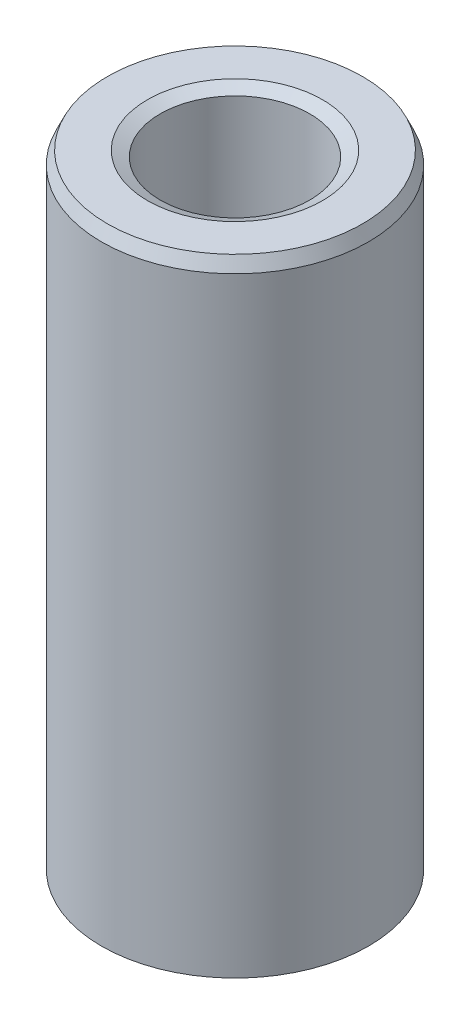
SolidWorks part; units mm, degrees
ref_plane "Front Plane" through (0, 0, 0) normal (0, 0, 1) x (1, 0, 0)
ref_plane "Top Plane" through (0, 0, 0) normal (0, 1, 0) x (1, 0, 0)
ref_plane "Right Plane" through (0, 0, 0) normal (1, 0, 0) x (0, 0, -1)
sketch "Sketch1" plane through (0, 0, 0) normal (0, 1, 0) x (1, 0, 0)
  circle A0 centre (0, 0) radius 20
  dimension "SLEEVE_OD" = 40
extrude "Boss-Extrude1" add sketch "Sketch1" along normal blind 94.1859
sketch "Sketch2" plane through (0, 0, 0) normal (0, 1, 0) x (1, 0, 0)
  circle A0 centre (0, 0) radius 11.2066
  dimension "BORE_D" = 22.4131
extrude "Cut-Extrude1" cut sketch "Sketch2" along normal through all
chamfer "Chamfer1" distance 1.9081 angle 24.715 4 edges at (0, 94.1859, 11.2066) (0, 0, 11.2066) (0, 0, 20) (0, 94.1859, 20) first distance on face at (0, 94.1859, 11.2066) first distance on face at (0, 0, 11.2066) first distance on face at (0, 94.1859, 20)
